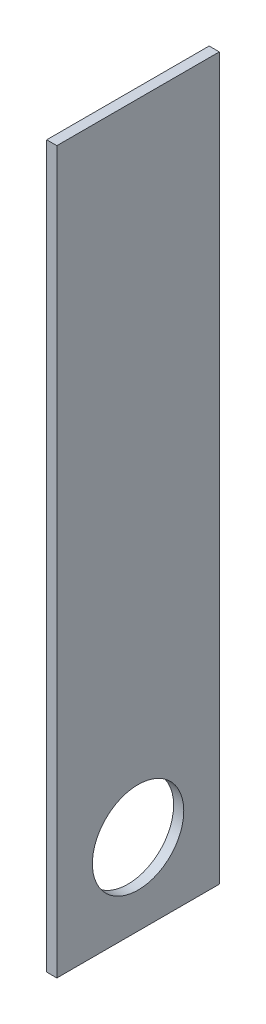
SolidWorks part; units mm, degrees
material "6063-O"
ref_plane "Front" through (0, 0, 0) normal (0, 0, 1) x (1, 0, 0)
ref_plane "Top" through (0, 0, 0) normal (0, 1, 0) x (1, 0, 0)
ref_plane "Right" through (0, 0, 0) normal (1, 0, 0) x (0, 0, -1)
sketch "Sketch1" plane through (0, 0, 0) normal (1, 0, 0) x (0, 0, -1)
  line L0 (0, 112.7125) -> (0, -112.7125) construction
  line L1 (-25.4, 112.7125) -> (25.4, 112.7125)
  line L2 (-25.4, 112.7125) -> (-25.4, -112.7125)
  line L3 (-25.4, -112.7125) -> (25.4, -112.7125)
  line L4 (25.4, 112.7125) -> (25.4, -112.7125)
  circle A0 centre (0, -87.3125) radius 14.2875
  point P4 (0, 0)
  dimension "D3" = 28.575
  dimension "D1" = 50.8
  dimension "D2" = 225.425
  dimension "D4" = 25.4
extrude "Boss-Extrude1" add sketch "Sketch1" along normal blind 3.175
